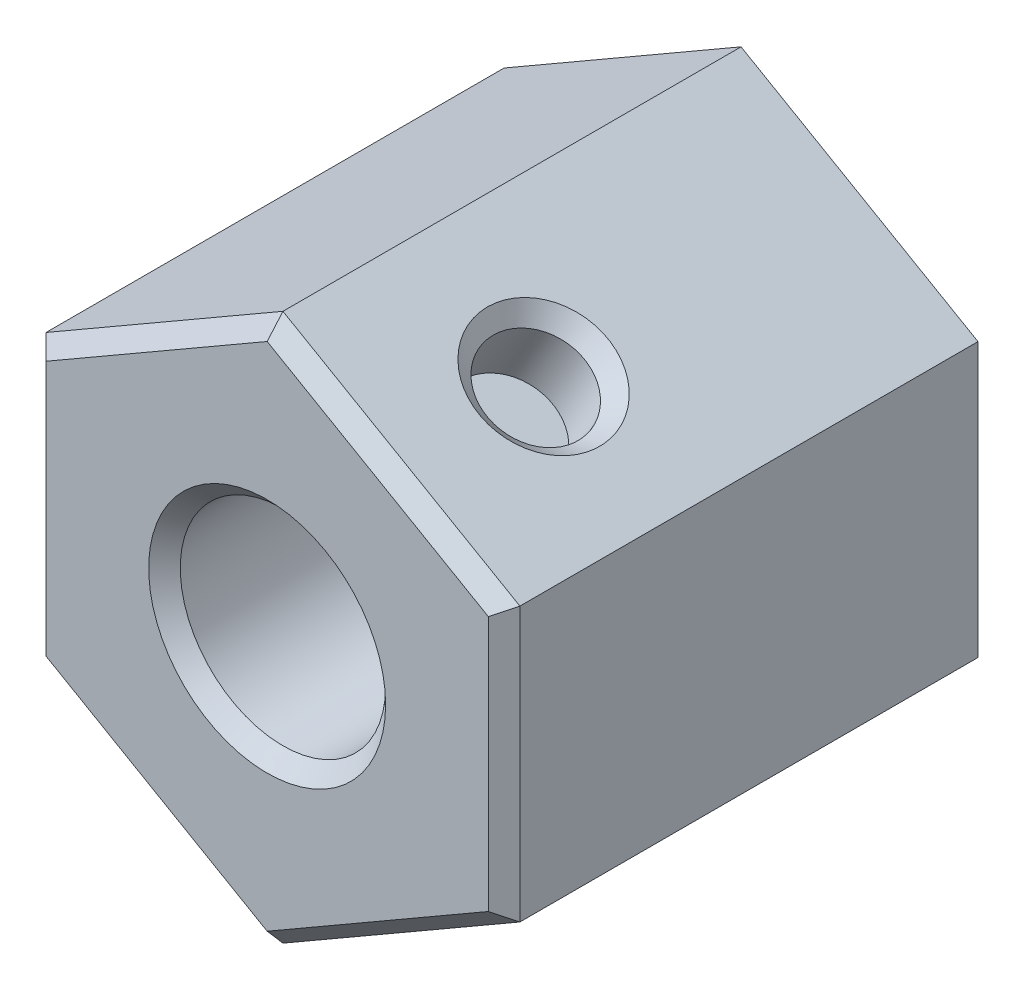
SolidWorks part; units mm, degrees
ref_plane "Front" through (0, 0, 0) normal (0, 0, 1) x (1, 0, 0)
ref_plane "Top" through (0, 0, 0) normal (0, 1, 0) x (1, 0, 0)
ref_plane "Right" through (0, 0, 0) normal (1, 0, 0) x (0, 0, -1)
sketch "Sketch1" plane through (0, 0, 0) normal (0, 0, 1) x (1, 0, 0)
  line L1 (0, 8.6603) -> (-7.5, 4.3301)
  line L2 (-7.5, 4.3301) -> (-7.5, -4.3301)
  line L3 (-7.5, -4.3301) -> (0, -8.6603)
  line L4 (0, -8.6603) -> (7.5, -4.3301)
  line L5 (7.5, -4.3301) -> (7.5, 4.3301)
  line L6 (7.5, 4.3301) -> (0, 8.6603)
  circle A0 centre (0, 0) radius 7.5 construction
  dimension "D1" = 15
extrude "Boss-Extrude1" add sketch "Sketch1" along normal blind 15
sketch "Sketch2" plane through (0, 0, 15) normal (0, 0, 1) x (1, 0, 0)
  circle A0 centre (0, 0) radius 3.25
  dimension "D1" = 6.5
extrude "Cut-Extrude1" cut sketch "Sketch2" against normal blind 15
sketch "Sketch3" plane through (0, 0, 0) normal (0, 0, -1) x (-1, 0, 0)
  line L0 (-7.5, 4.3301) -> (0, 8.6603) construction
  line L1 (0, 5.889) -> (-5.1, 2.9445)
  line L2 (-5.1, 2.9445) -> (-5.1, -2.9445)
  line L3 (-5.1, -2.9445) -> (0, -5.889)
  line L4 (0, -5.889) -> (5.1, -2.9445)
  line L5 (5.1, -2.9445) -> (5.1, 2.9445)
  line L6 (5.1, 2.9445) -> (0, 5.889)
  circle A0 centre (0, 0) radius 5.1 construction
  dimension "D1" = 10.2
extrude "Cut-Extrude2" cut sketch "Sketch3" against normal blind 2.5
sketch "Sketch4" plane through (3.75, 6.4952, 0) normal (0.5, 0.866, 0) x (0.866, -0.5, 0)
  line L0 (4.3301, 0) -> (-4.3301, 0) construction
  circle A0 centre (0, -10) radius 1.55
  point P5 (0, 0)
  dimension "D1" = 3.1
  dimension "D2" = 10
extrude "Cut-Extrude3" cut sketch "Sketch4" against normal blind 2.5
ref_axis "Axis1" through (0, 0, 2.5) along (0, 0, 1)
pattern_circular "CirPattern1" count 3 over 360 about axis through (0, 0, 15) along (0, 0, 1) of "Cut-Extrude3"
chamfer "Chamfer1" distance 0.5 angle 45 7 edges at (7.5, 0, 15) (3.75, -6.4952, 15) (-3.75, -6.4952, 15) (-7.5, 0, 15) (-3.75, 6.4952, 15) (3.75, 6.4952, 15) (3.25, 0, 15)
chamfer "Chamfer2" distance 0.5 angle 45 3 edges at (-7.5, -1.55, 10) (5.0923, -5.7202, 10) (2.4077, 7.2702, 10)
chamfer "Chamfer3" distance 0.5 angle 45 1 edges at (-3.25, 0, 2.5)
